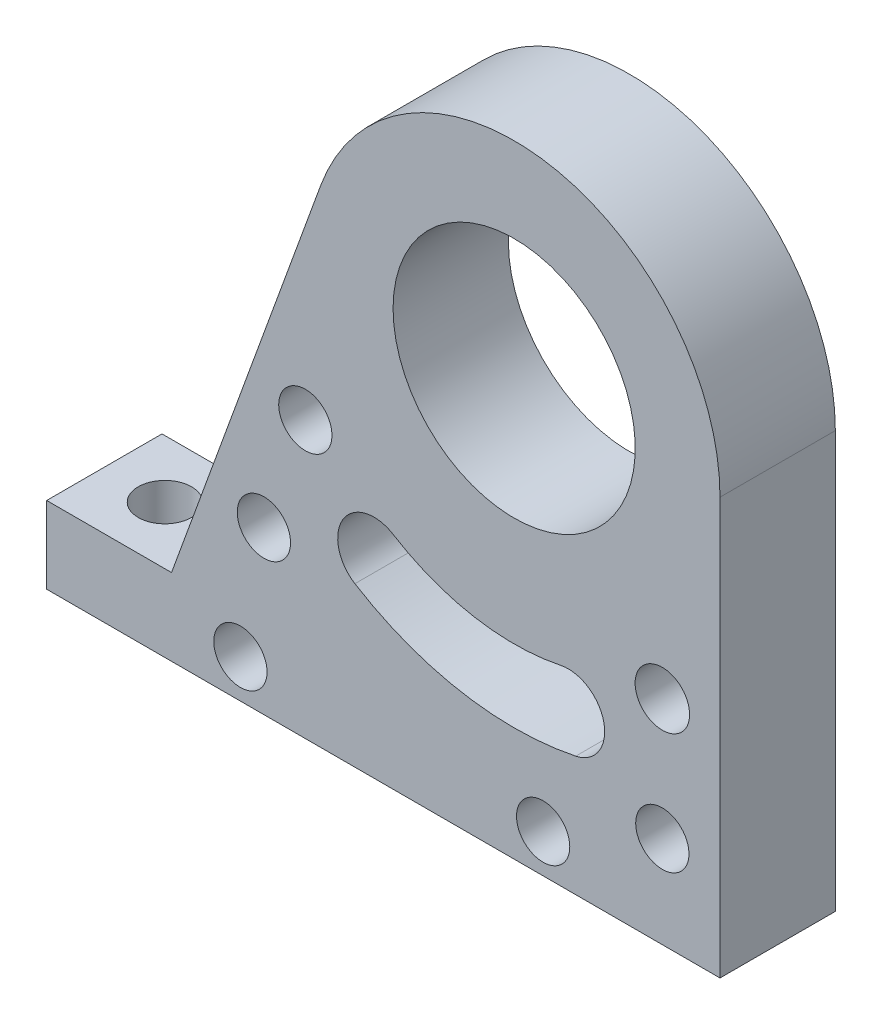
SolidWorks part; units mm, degrees
material "6061 Alloy"
ref_plane "Front Plane" through (0, 0, 0) normal (0, 0, 1) x (1, 0, 0)
ref_plane "Top Plane" through (0, 0, 0) normal (0, 1, 0) x (1, 0, 0)
ref_plane "Right Plane" through (0, 0, 0) normal (1, 0, 0) x (0, 0, -1)
sketch "Sketch1" plane through (0, 0, 0) normal (0, 0, 1) x (1, 0, 0)
  line L0 (-26.7836, -11.003) -> (22.5905, -28.9737) construction
  line L1 (0, 0) -> (17.7131, 0) construction
  line L2 (17, 0) -> (17, -34.3882)
  line L3 (-15.9748, 5.8143) -> (-30.6073, -34.3882)
  line L4 (17, -34.3882) -> (-30.6073, -34.3882)
  circle A0 centre (0, 0) radius 10
  arc A1 (-15.9748, 5.8143) -> (17, 0) centre (0, 0) cw
  dimension "D1" = 20
  dimension "D4" = 7
  dimension "D2" = 20
  dimension "D3" = 19.5
  dimension "D5" = 7
extrude "Boss-Extrude1" add sketch "Sketch1" along normal blind 9.525
sketch "Sketch2" plane through (0, 0, 0) normal (0, 0, 1) x (1, 0, 0)
  line L2 (12.2375, -26.8001) -> (12.2375, -16.8001) construction
  line L4 (-20.6657, -20.9984) -> (-17.2455, -11.6014) construction
  line L5 (-15.9748, 5.8143) -> (-30.6073, -34.3882) construction
  line L6 (17, 0) -> (17, -34.3882) construction
  circle A0 centre (12.2375, -26.8001) radius 2.2
  circle A1 centre (12.2375, -16.8001) radius 2.25
  circle A2 centre (-20.6657, -20.9984) radius 2.2
  circle A3 centre (-17.2455, -11.6014) radius 2.2
  arc A4 (-18.9556, -16.2999) -> (12.2375, -21.8001) centre (0, 0) ccw construction
  dimension "D3" = 4.4
  dimension "D6" = 4.4
  dimension "D7" = 25
  dimension "D1" = 4.7625
  dimension "D2" = 10
  dimension "D4" = 10
  dimension "D5" = 4.7625
extrude "M4_through" cut sketch "Sketch2" along normal up to surface (9.525 mm away) up to face at (-2.5357, -12.2819, 9.525)
sketch "Sketch4" plane through (0, 0, 9.525) normal (0, 0, 1) x (1, 0, 0)
  line L0 (-15.9748, 5.8143) -> (-30.6073, -34.3882) construction
  line L1 (17, -34.3882) -> (17, 0) construction
  arc A0 (-11.5723, -18.7105) -> (4.475, -21.5401) centre (0, 0) ccw construction
  arc A1 (-9.9942, -16.1591) -> (3.8648, -18.6028) centre (0, 0) ccw
  arc A2 (-13.1503, -21.2619) -> (5.0852, -24.4773) centre (0, 0) ccw
  arc A3 (-9.9942, -16.1591) -> (-13.1503, -21.2619) centre (-11.5723, -18.7105) ccw
  arc A4 (3.8648, -18.6028) -> (5.0852, -24.4773) centre (4.475, -21.5401) cw
  dimension "D1" = 22
  dimension "D2" = 6
  dimension "D3" = 3
  dimension "D4" = 12.525
  dimension "D5" = 12.525
extrude "Cut-Extrude2" cut sketch "Sketch4" against normal up to surface (9.525 mm away) up to face at (14.4375, -26.8001, 0)
sketch "Sketch6" plane through (0, 0, 9.525) normal (0, 0, 1) x (1, 0, 0)
  line L0 (-30.6073, -34.3882) -> (-38.6073, -34.3882)
  line L1 (-38.6073, -34.3882) -> (-38.6073, -28.0382)
  line L2 (-38.6073, -28.0382) -> (-28.2961, -28.0382)
  line L3 (-15.9748, 5.8143) -> (-30.6073, -34.3882) construction
  line L4 (-28.2961, -28.0382) -> (-30.6073, -34.3882)
  dimension "D1" = 8
  dimension "D2" = 6.35
extrude "Boss-Extrude2" add sketch "Sketch6" against normal up to surface (9.525 mm away) up to face at (-3.588, -20.3485, 0)
sketch "Sketch5" plane through (0, -34.3882, 0) normal (0, -1, 0) x (1, 0, 0)
  line L0 (-38.6073, 4.7625) -> (17, 4.7625) construction
  line L2 (17, 9.525) -> (17, 0) construction
  line L3 (-38.6073, 0) -> (-38.6073, 9.525) construction
  circle A0 centre (-33.6073, 4.7625) radius 2.2
  circle A1 centre (-8.6073, 4.7625) radius 2.2
  dimension "D1" = 4.4
  dimension "D2" = 4.4
  dimension "D3" = 5
  dimension "D4" = 25
extrude "M5_DRILL" cut sketch "Sketch5" against normal blind 8
sketch "Sketch7" plane through (0, 0, 9.525) normal (0, 0, 1) x (1, 0, 0)
  line L0 (-38.6073, -31.2132) -> (-22.6073, -31.2132) construction
  line L1 (-38.6073, -28.0382) -> (-38.6073, -34.3882) construction
  circle A0 centre (-22.6073, -31.2132) radius 2.2
  circle A1 centre (2.3927, -31.2132) radius 2.2
  dimension "D1" = 4.4
  dimension "D3" = 2
  dimension "D2" = 16
extrude "M4_through2" cut sketch "Sketch7" against normal up to surface (9.525 mm away) up to face at (-3.588, -20.3485, 0)
